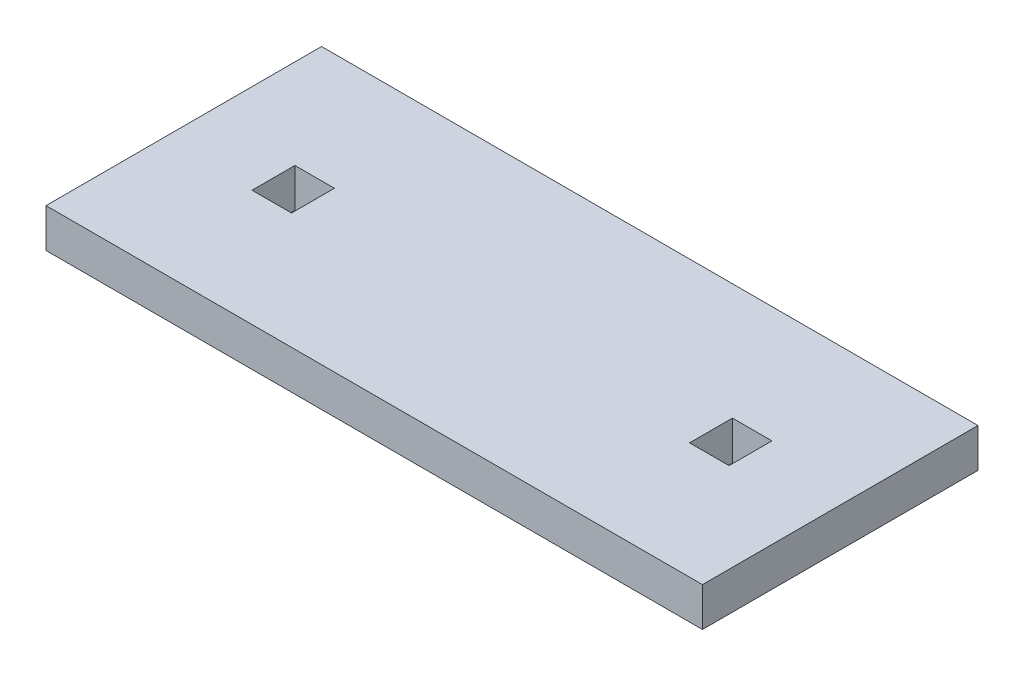
SolidWorks part; units mm, degrees
material "6061 Alloy"
ref_plane "Front Plane" through (0, 0, 0) normal (0, 0, 1) x (1, 0, 0)
ref_plane "Top Plane" through (0, 0, 0) normal (0, 1, 0) x (1, 0, 0)
ref_plane "Right Plane" through (0, 0, 0) normal (1, 0, 0) x (0, 0, -1)
sketch "Sketch1" plane through (0, 0, 0) normal (0, 1, 0) x (1, 0, 0)
  line L0 (107.2, 90) -> (107.2, 0) construction
  line L1 (0, 0) -> (214.4, 0)
  line L2 (0, 0) -> (0, 90)
  line L3 (0, 90) -> (214.4, 90)
  line L4 (214.4, 0) -> (214.4, 90)
  line L5 (29.3, 52) -> (42.2, 52)
  line L6 (29.3, 52) -> (29.3, 38)
  line L7 (29.3, 38) -> (42.2, 38)
  line L8 (42.2, 52) -> (42.2, 38)
  line L9 (185.1, 38) -> (172.2, 38)
  line L10 (172.2, 52) -> (172.2, 38)
  line L11 (185.1, 52) -> (172.2, 52)
  line L12 (185.1, 52) -> (185.1, 38)
  dimension "D1" = 214.4
  dimension "D2" = 90
  dimension "D3" = 38
  dimension "D4" = 38
  dimension "D5" = 65
  dimension "D6" = 12.9
extrude "Boss-Extrude1" add sketch "Sketch1" along normal blind 12.7
